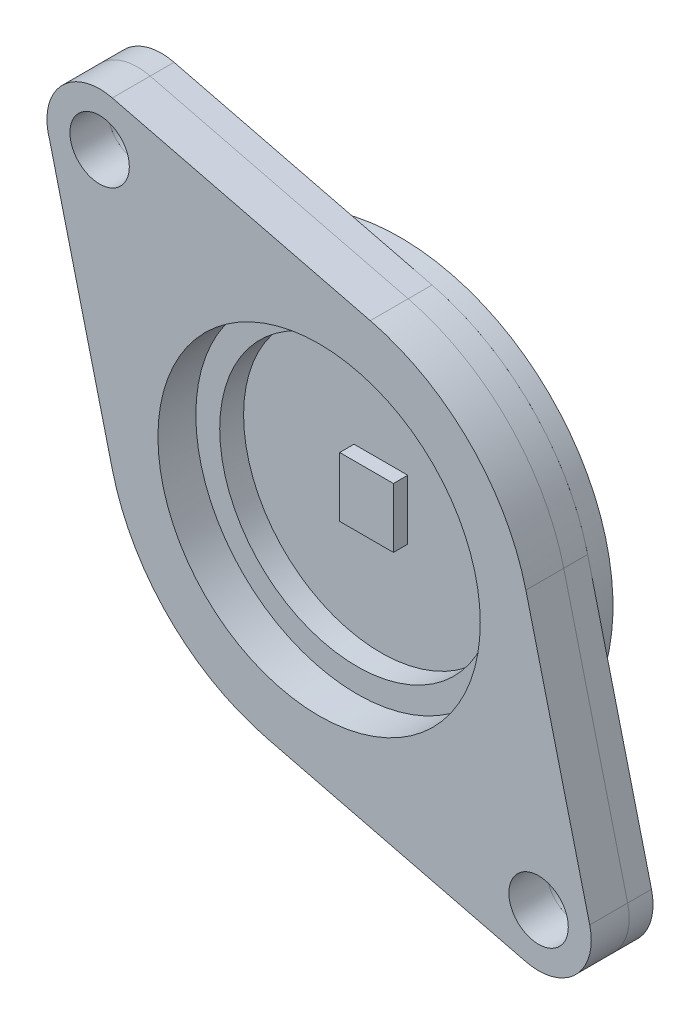
SolidWorks part; units mm, degrees
ref_plane "Front Plane" through (0, 0, 0) normal (0, 0, 1) x (1, 0, 0)
ref_plane "Top Plane" through (0, 0, 0) normal (0, 1, 0) x (1, 0, 0)
ref_plane "Right Plane" through (0, 0, 0) normal (1, 0, 0) x (0, 0, -1)
sketch "Sketch1" plane through (0, 0, 0) normal (0, 0, 1) x (1, 0, 0)
  line L0 (-22.5732, 16.9951) -> (-17.3222, -4.2762)
  line L1 (23.8125, -23.8125) -> (-23.8125, -23.8125) construction
  line L2 (23.8125, -23.8125) -> (23.8125, 23.8125) construction
  line L3 (23.8125, 23.8125) -> (-23.8125, 23.8125) construction
  line L4 (-23.8125, -23.8125) -> (-23.8125, 23.8125) construction
  line L5 (23.8125, -23.8125) -> (-23.8125, 23.8125) construction
  line L6 (23.8125, 23.8125) -> (-23.8125, -23.8125) construction
  line L7 (-17.3245, 22.6685) -> (4.2867, 17.3196)
  line L8 (17.3196, 4.2867) -> (22.6685, -17.3245)
  line L9 (-4.2867, -17.3196) -> (17.3245, -22.6685)
  circle A0 centre (0, 0) radius 21.75 construction
  circle A1 centre (0, 0) radius 26 construction
  circle A2 centre (-18.3848, 18.3848) radius 2.413 construction
  circle A3 centre (18.3848, -18.3848) radius 3.0643 construction
  arc A4 (-17.3245, 22.6685) -> (-22.5732, 16.9951) centre (-18.3848, 18.3848) ccw
  arc A5 (17.3245, -22.6685) -> (22.6685, -17.3245) centre (18.3848, -18.3848) ccw
  arc A6 (-17.3222, -4.2762) -> (-4.2867, -17.3196) centre (0, 0) ccw
  circle A7 centre (0, 0) radius 13.5
  arc A8 (17.3196, 4.2867) -> (4.2867, 17.3196) centre (0, 0) ccw
  dimension "D1" = 43.5
  dimension "D2" = 52
  dimension "D4" = 4.826
  dimension "D5" = 27
  dimension "D6" = 2
  dimension "D3" = 47.625
extrude "Boss-Extrude1" add sketch "Sketch1" along normal blind 3.175
sketch "Sketch2" plane through (0, 0, 3.175) normal (0, 0, 1) x (1, 0, 0)
  point P0 (-18.3848, 18.3848)
  point P3 (18.3848, -18.3848)
hole_wizard "#10 Clearance Hole1" positions "Sketch2" profile "Sketch3" hole size "#10" standard "ANSI Inch" end condition through all
sketch "Sketch3" plane through (-18.3848, 18.3848, 3.175) normal (1, 0, 0) x (0, -1, 0)
  line L0 (0, 0) -> (0, 3.175)
  line L1 (0, 3.175) -> (2.4892, 3.175)
  line L2 (2.4892, 3.175) -> (2.4892, 0)
  line L5 (2.4892, 0) -> (0, 0)
  line L11 (0, -6.35) -> (0, 107.95) construction
  dimension "Thru Hole Dia." = 4.9784
  dimension "Thru Hole Depth" = 3.175
sketch "Sketch6" plane through (0, 0, 0) normal (0, 0, -1) x (-1, 0, 0)
  line L4 (17.3245, 22.6685) -> (-4.2867, 17.3196)
  line L5 (-17.3196, 4.2867) -> (-22.6685, -17.3245)
  line L6 (-17.3245, -22.6685) -> (4.2867, -17.3196)
  line L7 (17.3222, -4.2762) -> (22.5732, 16.9951)
  line L8 (17.3245, 22.6685) -> (-4.2867, 17.3196)
  line L9 (-17.3196, 4.2867) -> (-22.6685, -17.3245)
  line L10 (-17.3245, -22.6685) -> (4.2867, -17.3196)
  line L11 (17.3222, -4.2762) -> (22.5732, 16.9951)
  circle A0 centre (0, 0) radius 11.5
  circle A1 centre (0, 0) radius 13.5 construction
  circle A3 centre (-18.3848, -18.3848) radius 2.4892
  circle A4 centre (-18.3848, -18.3848) radius 2.4892
  circle A5 centre (18.3848, 18.3848) radius 2.4892
  circle A6 centre (18.3848, 18.3848) radius 2.4892
  arc A10 (22.5732, 16.9951) -> (17.3245, 22.6685) centre (18.3848, 18.3848) ccw
  arc A11 (-4.2867, 17.3196) -> (-17.3196, 4.2867) centre (0, 0) ccw
  arc A12 (-22.6685, -17.3245) -> (-17.3245, -22.6685) centre (-18.3848, -18.3848) ccw
  arc A13 (4.2867, -17.3196) -> (17.3222, -4.2762) centre (0, 0) ccw
  arc A14 (22.5732, 16.9951) -> (17.3245, 22.6685) centre (18.3848, 18.3848) ccw
  arc A15 (-4.2867, 17.3196) -> (-17.3196, 4.2867) centre (0, 0) ccw
  arc A16 (-22.6685, -17.3245) -> (-17.3245, -22.6685) centre (-18.3848, -18.3848) ccw
  arc A17 (4.2867, -17.3196) -> (17.3222, -4.2762) centre (0, 0) ccw
  dimension "D1" = 2
  dimension "D2" = 0
  dimension "D3" = 0
  dimension "D4" = 0
extrude "Boss-Extrude4" add sketch "Sketch6" along normal blind 2 separate body
sketch "Sketch4" plane through (0, 0, -2) normal (0, 0, -1) x (-1, 0, 0)
  line L4 (17.3245, 22.6685) -> (-4.2867, 17.3196)
  line L5 (-17.3196, 4.2867) -> (-22.6685, -17.3245)
  line L6 (-17.3245, -22.6685) -> (4.2867, -17.3196)
  line L7 (17.3222, -4.2762) -> (22.5732, 16.9951)
  arc A10 (22.5732, 16.9951) -> (17.3245, 22.6685) centre (18.3848, 18.3848) ccw
  arc A11 (-4.2867, 17.3196) -> (-17.3196, 4.2867) centre (0, 0) ccw
  arc A12 (-22.6685, -17.3245) -> (-17.3245, -22.6685) centre (-18.3848, -18.3848) ccw
  arc A13 (4.2867, -17.3196) -> (17.3222, -4.2762) centre (0, 0) ccw
  arc A15 (17.3222, -4.2762) -> (4.2867, -17.3196) centre (0, 0) ccw
  arc A17 (4.2867, -17.3196) -> (17.3222, -4.2762) centre (0, 0) ccw
  dimension "D4" = 0
extrude "Boss-Extrude2" add sketch "Sketch4" along normal blind 1.6 separate body
sketch "Sketch5" plane through (0, 0, -2) normal (0, 0, 1) x (1, 0, 0)
  line L1 (2.25, -2.5) -> (-2.25, -2.5)
  line L2 (2.25, -2.5) -> (2.25, 2.5)
  line L3 (2.25, 2.5) -> (-2.25, 2.5)
  line L4 (-2.25, -2.5) -> (-2.25, 2.5)
  line L5 (2.25, -2.5) -> (-2.25, 2.5) construction
  line L6 (2.25, 2.5) -> (-2.25, -2.5) construction
  point P0 (0, 0)
  dimension "D1" = 4.5
  dimension "D2" = 5
extrude "Boss-Extrude3" add sketch "Sketch5" along normal blind 1.2 separate body
